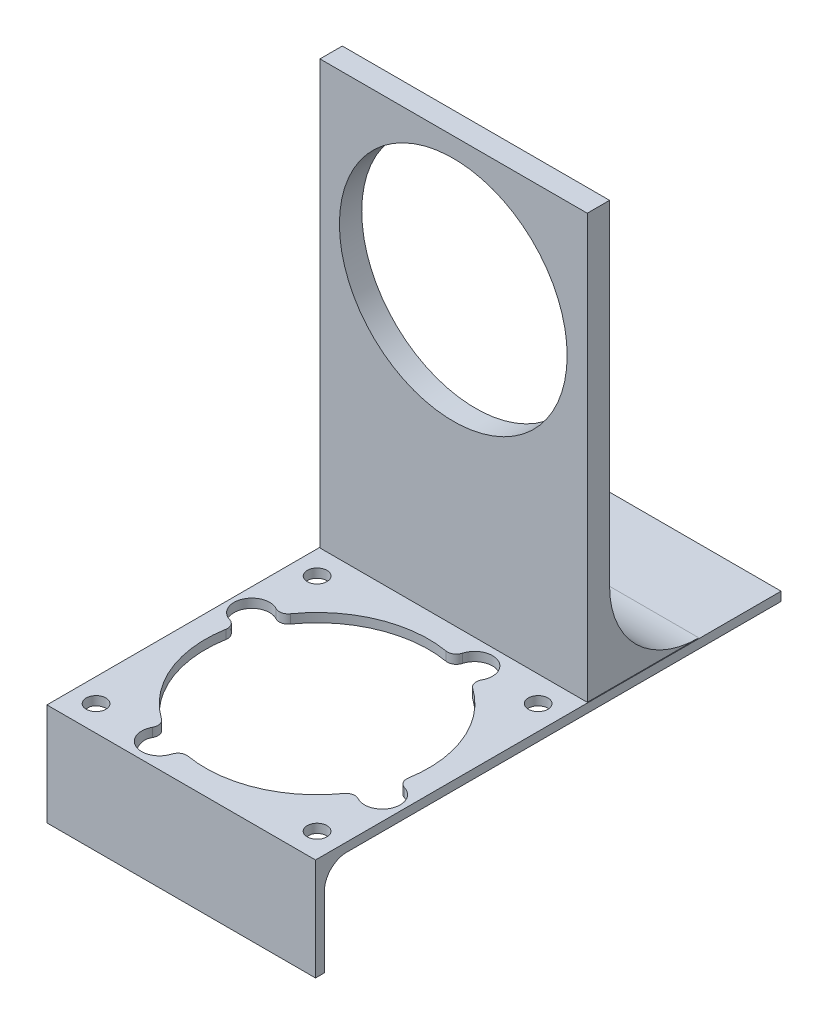
SolidWorks part; units mm, degrees
ref_plane "前视基准面" through (0, 0, 0) normal (0, 0, 1) x (1, 0, 0)
ref_plane "上视基准面" through (0, 0, 0) normal (0, 1, 0) x (1, 0, 0)
ref_plane "右视基准面" through (0, 0, 0) normal (1, 0, 0) x (0, 0, -1)
other "Configuration Table"
sketch "草图2" plane through (0, 0, -61) normal (0, 0, -1) x (-1, 0, 0)
  line L1 (-30, -65) -> (29.8536, -65)
  line L2 (-30, -65) -> (-30, 29.8536)
  line L3 (-30, 29.8536) -> (29.8536, 29.8536)
  line L4 (29.8536, -65) -> (29.8536, 29.8536)
  arc A0 (30, 29.5) -> (29.5, 30) centre (29.5, 29.5) ccw construction
  circle A1 centre (0, 0) radius 25.5
extrude "凸台-拉伸1" add sketch "草图2" along normal blind 5
sketch "草图3" plane through (0, -65, 0) normal (0, -1, 0) x (1, 0, 0)
  line L0 (-30, 0) -> (-30, -4.5) construction
  line L1 (-30, -104.2586) -> (30.1464, -104.2586)
  line L2 (-30, -104.2586) -> (-30, 0)
  line L3 (-30, 0) -> (30.1464, 0)
  line L4 (30.1464, -104.2586) -> (30.1464, 0)
  circle A0 centre (-24.7487, -5.7513) radius 2.2
  circle A1 centre (24.7487, -5.7513) radius 2.2
  circle A2 centre (24.7487, -55.2487) radius 2.2
  circle A3 centre (-24.7487, -55.2487) radius 2.2
  arc A4 (-26.0554, -36.9897) -> (-24.6395, -34.73) centre (-26.6107, -35.0684) ccw construction
  arc A5 (-26.0554, -36.9897) -> (-23.0129, -44.335) centre (-24.9447, -40.8325) ccw construction
  arc A6 (-20.4138, -44.9317) -> (-23.0129, -44.335) centre (-22.0469, -46.0863) ccw construction
  arc A7 (-20.4138, -44.9317) -> (4.23, -55.1395) centre (0, -30.5) ccw construction
  arc A8 (6.4897, -56.5554) -> (4.23, -55.1395) centre (4.5684, -57.1107) ccw construction
  arc A9 (6.4897, -56.5554) -> (13.835, -53.5129) centre (10.3325, -55.4447) ccw construction
  arc A10 (14.4317, -50.9138) -> (13.835, -53.5129) centre (15.5863, -52.5469) ccw construction
  arc A11 (14.4317, -50.9138) -> (24.6395, -26.27) centre (0, -30.5) ccw construction
  arc A12 (26.0554, -24.0103) -> (24.6395, -26.27) centre (26.6107, -25.9316) ccw construction
  arc A13 (26.0554, -24.0103) -> (23.0129, -16.665) centre (24.9447, -20.1675) ccw construction
  arc A14 (20.4138, -16.0683) -> (23.0129, -16.665) centre (22.0469, -14.9137) ccw construction
  arc A15 (20.4138, -16.0683) -> (-4.23, -5.8605) centre (0, -30.5) ccw construction
  arc A16 (-6.4897, -4.4446) -> (-4.23, -5.8605) centre (-4.5684, -3.8893) ccw construction
  arc A17 (-6.4897, -4.4446) -> (-13.835, -7.4871) centre (-10.3325, -5.5553) ccw construction
  arc A18 (-14.4317, -10.0862) -> (-13.835, -7.4871) centre (-15.5863, -8.4531) ccw construction
  arc A19 (-14.4317, -10.0862) -> (-24.6395, -34.73) centre (0, -30.5) ccw construction
  arc A20 (-26.0554, -36.9897) -> (-24.6395, -34.73) centre (-26.6107, -35.0684) ccw
  arc A21 (-26.0554, -36.9897) -> (-23.0129, -44.335) centre (-24.9447, -40.8325) ccw
  arc A22 (-20.4138, -44.9317) -> (-23.0129, -44.335) centre (-22.0469, -46.0863) ccw
  arc A23 (-20.4138, -44.9317) -> (4.23, -55.1395) centre (0, -30.5) ccw
  arc A24 (6.4897, -56.5554) -> (4.23, -55.1395) centre (4.5684, -57.1107) ccw
  arc A25 (6.4897, -56.5554) -> (13.835, -53.5129) centre (10.3325, -55.4447) ccw
  arc A26 (14.4317, -50.9138) -> (13.835, -53.5129) centre (15.5863, -52.5469) ccw
  arc A27 (14.4317, -50.9138) -> (24.6395, -26.27) centre (0, -30.5) ccw
  arc A28 (26.0554, -24.0103) -> (24.6395, -26.27) centre (26.6107, -25.9316) ccw
  arc A29 (26.0554, -24.0103) -> (23.0129, -16.665) centre (24.9447, -20.1675) ccw
  arc A30 (20.4138, -16.0683) -> (23.0129, -16.665) centre (22.0469, -14.9137) ccw
  arc A31 (20.4138, -16.0683) -> (-4.23, -5.8605) centre (0, -30.5) ccw
  arc A32 (-6.4897, -4.4446) -> (-4.23, -5.8605) centre (-4.5684, -3.8893) ccw
  arc A33 (-6.4897, -4.4446) -> (-13.835, -7.4871) centre (-10.3325, -5.5553) ccw
  arc A34 (-14.4317, -10.0862) -> (-13.835, -7.4871) centre (-15.5863, -8.4531) ccw
  arc A35 (-14.4317, -10.0862) -> (-24.6395, -34.73) centre (0, -30.5) ccw
  point P45 (-30, 0)
extrude "凸台-拉伸2" add sketch "草图3" along normal blind 2
fillet "圆角1" radius 20 1 edges at (0.0732, -65, -66)
sketch "草图4" plane through (0, 0, 0) normal (0, 0, 1) x (1, 0, 0)
  line L1 (-30, -67) -> (30.1464, -67)
  line L2 (-30, -67) -> (-30, -87.8915)
  line L3 (-30, -87.8915) -> (30.1464, -87.8915)
  line L4 (30.1464, -67) -> (30.1464, -87.8915)
  point P5 (30.1464, -67)
extrude "凸台-拉伸3" add sketch "草图4" against normal blind 2
fillet "圆角2" radius 5 1 edges at (10.8235, -67, -2)
fillet "圆角3" radius 5 1 edges at (-21.0828, -67, -2)
